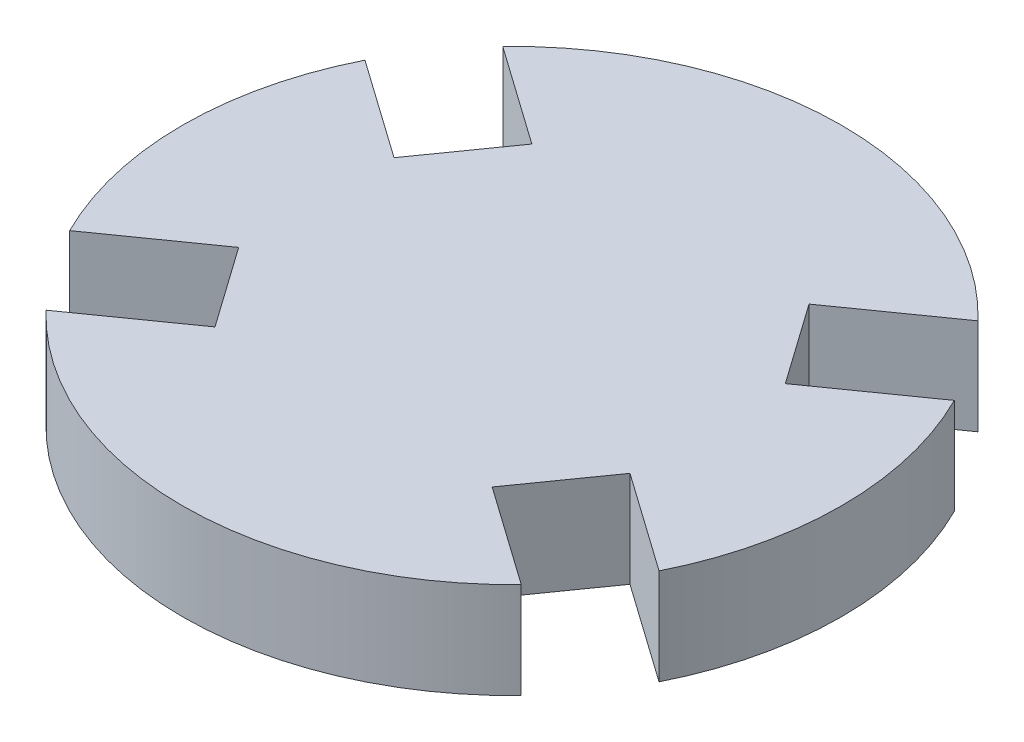
SolidWorks part; units mm, degrees
ref_plane "Alzado" through (0, 0, 0) normal (0, 0, 1) x (1, 0, 0)
ref_plane "Planta" through (0, 0, 0) normal (0, 1, 0) x (1, 0, 0)
ref_plane "Vista lateral" through (0, 0, 0) normal (1, 0, 0) x (0, 0, -1)
sketch "Croquis1" plane through (0, 0, 0) normal (0, 1, 0) x (1, 0, 0)
  circle A0 centre (0, 0) radius 12
  dimension "D1" = 24
extrude "Saliente-Extruir1" add sketch "Croquis1" along normal blind 3.5
sketch "Croquis3" plane through (0, 3.5, 0) normal (0, 1, 0) x (1, 0, 0)
  line L0 (0, 0) -> (0, 12) construction
  line L1 (0, 0) -> (12, 0) construction
  line L2 (0, 0) -> (9.8013, 6.9235) construction
  line L8 (14.5561, 8.0785) -> (7.1235, 2.8281)
  line L9 (14.5561, 8.0785) -> (12.4791, 11.0189)
  line L10 (12.4791, 11.0189) -> (5.0464, 5.7685)
  line L11 (7.1235, 2.8281) -> (5.0464, 5.7685)
  line L12 (14.5561, 8.0785) -> (5.0464, 5.7685) construction
  line L13 (12.4791, 11.0189) -> (7.1235, 2.8281) construction
  line L15 (-14.5561, -8.0785) -> (-5.0464, -5.7685) construction
  line L16 (-12.4791, -11.0189) -> (-7.1235, -2.8281) construction
  line L17 (-5.0464, -5.7685) -> (-7.1235, -2.8281)
  line L18 (-14.5561, -8.0785) -> (-7.1235, -2.8281)
  line L19 (-12.4791, -11.0189) -> (-14.5561, -8.0785)
  line L20 (-12.4791, -11.0189) -> (-5.0464, -5.7685)
  line L21 (12.4791, -11.0189) -> (7.1235, -2.8281) construction
  line L22 (14.5561, -8.0785) -> (5.0464, -5.7685) construction
  line L23 (-12.4791, 11.0189) -> (-7.1235, 2.8281) construction
  line L24 (-14.5561, 8.0785) -> (-5.0464, 5.7685) construction
  line L25 (12.4791, -11.0189) -> (5.0464, -5.7685)
  line L26 (12.4791, -11.0189) -> (14.5561, -8.0785)
  line L27 (14.5561, -8.0785) -> (7.1235, -2.8281)
  line L28 (5.0464, -5.7685) -> (7.1235, -2.8281)
  line L29 (-7.1235, 2.8281) -> (-5.0464, 5.7685)
  line L30 (-12.4791, 11.0189) -> (-5.0464, 5.7685)
  line L31 (-14.5561, 8.0785) -> (-12.4791, 11.0189)
  line L32 (-14.5561, 8.0785) -> (-7.1235, 2.8281)
  circle A0 centre (0, 0) radius 12 construction
  dimension "D2" = 9.1
  dimension "D3" = 3.6
  dimension "D1" = 35.237
extrude "Cortar-Extruir1" cut sketch "Croquis3" against normal blind 3.5
equation "\"dface\"=60"
equation "\"joind\"=9"
equation "\"P\"=.4"
equation "\"thickness\"=3.5"
equation "\"D1@Croquis1\" = \"P\" * \"dface\""
equation "\"D1@Saliente-Extruir1\"=\"thickness\""
equation "\"D2@Croquis3\"=\"joind\"+\"clear\""
equation "\"D3@Croquis3\"=\"thickness\"+\"clear\""
equation "\"clear\"=.1"
equation "\"D1@Cortar-Extruir1\"=\"thickness\""
